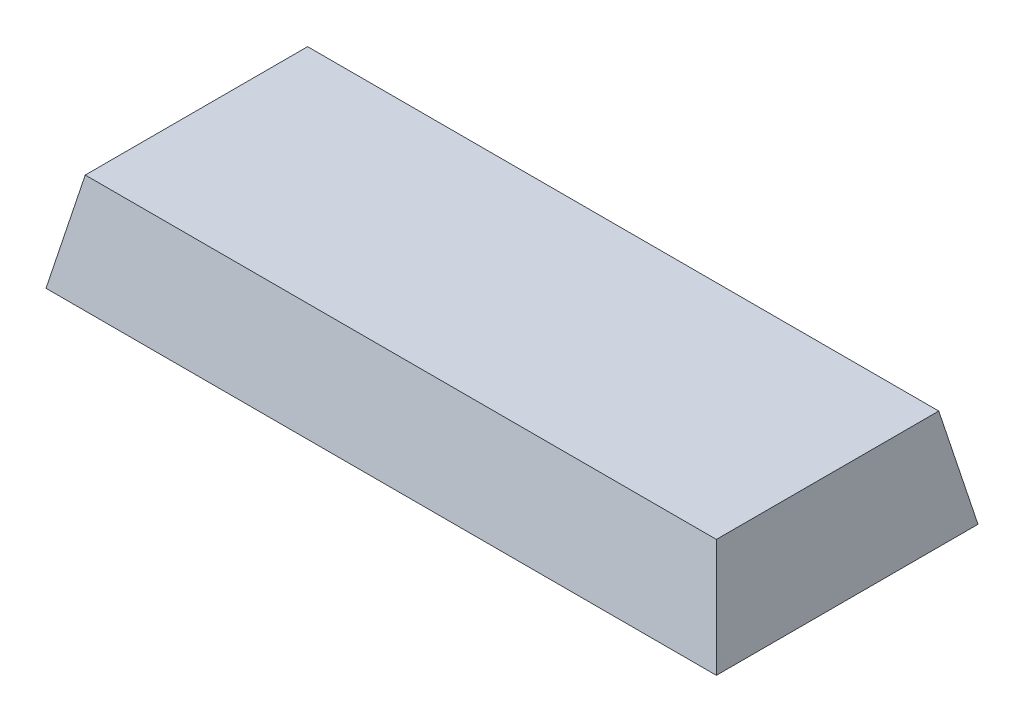
SolidWorks part; units mm, degrees
ref_plane "Front Plane" through (0, 0, 0) normal (0, 0, 1) x (1, 0, 0)
ref_plane "Top Plane" through (0, 0, 0) normal (0, 1, 0) x (1, 0, 0)
ref_plane "Right Plane" through (0, 0, 0) normal (1, 0, 0) x (0, 0, -1)
sketch "Sketch1" plane through (0, 0, 0) normal (0, 1, 0) x (1, 0, 0)
  line L1 (0, 0) -> (20.5, 0)
  line L2 (0, 0) -> (0, 8)
  line L3 (0, 8) -> (20.5, 8)
  line L4 (20.5, 0) -> (20.5, 8)
  dimension "D1" = 8
  dimension "D2" = 20.5
extrude "Boss-Extrude1" add sketch "Sketch1" along normal blind 3
sketch "Sketch2" plane through (0, 0, 0) normal (0, 0, 1) x (1, 0, 0)
  line L0 (0, 0) -> (0.6, 3)
  line L1 (0, 3) -> (20.5, 3) construction
  line L2 (0.6, 3) -> (0, 3)
  line L3 (0, 3) -> (0, 0)
  line L4 (20.5, 0) -> (19.9, 3)
  line L5 (19.9, 3) -> (20.5, 3)
  line L6 (20.5, 3) -> (20.5, 0)
  dimension "D1" = 0.6
  dimension "D2" = 0.6
extrude "Cut-Extrude1" cut sketch "Sketch2" against normal through all both and the other way through all
sketch "Sketch3" plane through (0, 0, 0) normal (1, 0, 0) x (0, 0, -1)
  line L0 (0, 0) -> (0.6, 3)
  line L1 (8, 3) -> (0, 3) construction
  line L2 (0.6, 3) -> (0, 3)
  line L3 (0, 3) -> (0, 0)
  line L4 (8, 3) -> (7.4, 3)
  line L5 (7.4, 3) -> (8, 0)
  line L6 (8, 3) -> (8, 0)
  dimension "D1" = 0.6
  dimension "D2" = 0.6
extrude "Cut-Extrude2" cut sketch "Sketch3" along normal through all both and the other way through all
sketch "Sketch4" plane through (0, 0, 0) normal (0, -1, 0) x (1, 0, 0)
  line L1 (10.25, 0) -> (10.25, -8) construction
  line L2 (20.5, -8) -> (0, -8) construction
  line L3 (0, 0) -> (20.5, 0) construction
  circle A0 centre (10.25, -3.75) radius 1.8
  dimension "D1" = 3.6
  dimension "D2" = 0
  dimension "D3" = 3.75
extrude "Cut-Extrude3" cut sketch "Sketch4" against normal blind 0.8
sketch "Sketch5" plane through (0, 0, 0) normal (0, -1, 0) x (1, 0, 0)
  line L5 (0, 0) -> (20.5, 0) construction
  line L6 (6.25, -8) -> (14.25, -8)
  line L7 (6.25, -8) -> (6.25, -7)
  line L8 (6.25, -7) -> (14.25, -7)
  line L9 (14.25, -8) -> (14.25, -7)
  point P2 (10.25, 0)
  dimension "D1" = 1
  dimension "D2" = 4
  dimension "D3" = 4
extrude "Boss-Extrude2" add sketch "Sketch5" along normal blind 2
fillet "Fillet1" radius 4 2 edges at (14.25, -2, -7.5) (6.25, -2, -7.5)
